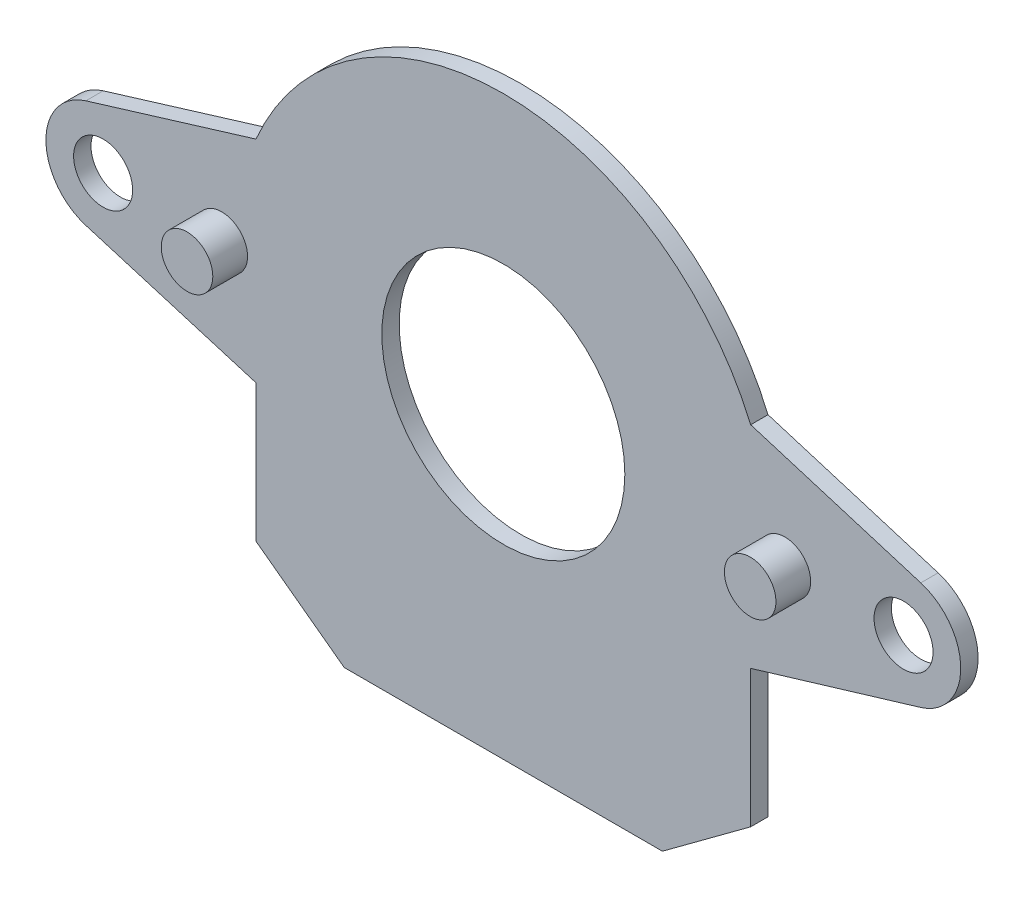
SolidWorks part; units mm, degrees
material "PETG"
ref_plane "Front Plane" through (0, 0, 0) normal (0, 0, 1) x (1, 0, 0)
ref_plane "Top Plane" through (0, 0, 0) normal (0, 1, 0) x (1, 0, 0)
ref_plane "Right Plane" through (0, 0, 0) normal (1, 0, 0) x (0, 0, -1)
sketch "Sketch1" plane through (0, 0, 0) normal (0, 0, 1) x (1, 0, 0)
  line L1 (14.25, -13.9625) -> (14.25, 6.0982)
  line L2 (-14.25, -13.9625) -> (-14.25, 6.0982)
  line L3 (-14.25, -13.9625) -> (-9.165, -17.722)
  line L4 (-9.165, -17.722) -> (9.165, -17.722)
  line L5 (9.165, -17.722) -> (14.25, -13.9625)
  line L6 (-14.25, -6.056) -> (-24.0362, -3.1122)
  line L7 (0, 3.4797) -> (0, 50003.4797) construction
  line L8 (-24.0485, 3.1085) -> (-14.25, 6.0982)
  line L9 (24.0485, 3.1085) -> (14.25, 6.0982)
  line L10 (14.25, -6.056) -> (24.0362, -3.1122)
  arc A0 (14.25, 6.0982) -> (-14.25, 6.0982) centre (0, 0) ccw
  circle A1 centre (0, 0) radius 7
  arc A2 (-24.0485, 3.1085) -> (-24.0362, -3.1122) centre (-23.1, 0) ccw
  arc A3 (24.0485, 3.1085) -> (24.0362, -3.1122) centre (23.1, 0) cw
  dimension "D1" = 28.5
  dimension "D2" = 15.5
  dimension "D7" = 14
  dimension "D8" = 6.056
  dimension "D10" = 3.25
  dimension "D4" = 17.722
  dimension "D5" = 13.9625
  dimension "D6" = 18.33
  dimension "D9" = 23.1
extrude "Boss-Extrude1" add sketch "Sketch1" along normal blind 1 contours L4 L7 A1 A0 L2 L3 | L8 A2 L6 L2 | L7 L4 L5 L1 A0 A1 | A3 L9 L1 L10 region at (11.4473, -15.4903, 0) region at (19.2892, 0.0104, 0) region at (-19.2892, 0.0104, 0)
sketch "Sketch2" plane through (0, 0, 1) normal (0, 0, 1) x (1, 0, 0)
  line L0 (0, -1.1396) -> (0, 49998.8604) construction
  circle A6 centre (-16.22, 0) radius 1.485
  circle A7 centre (-23.055, 0) radius 1.7
  circle A8 centre (23.055, 0) radius 1.7
  circle A9 centre (16.22, 0) radius 1.485
  dimension "D1" = 2.97
  dimension "D2" = 3.4
  dimension "D3" = 23.055
  dimension "D4" = 16.22
extrude "Boss-Extrude2" add sketch "Sketch2" along normal blind 2 contours A6 | A9 region at (-16.22, 0, 1)
extrude "Cut-Extrude1" cut sketch "Sketch2<5>" against normal through all contours A7 | A8 region at (-23.055, 0, 1) region at (23.055, 0, 1)
sketch "Sketch2<5>" plane through (0, 0, 1) normal (0, 0, 1) x (1, 0, 0) same geometry as "Sketch2"
equation "\"tol_dia_id_intfc\" = 0.0200mm ' For hole diameters - Interference fit"
equation "\"tol_dia_id_slip\"  = 0.0300mm ' For hole diameters - Slip fit"
equation "\"tol_dia_id_clear\" = 0.0500mm ' For hole diameters - Clearance fit"
equation "\"tol_dia_od_intfc\" = 0.0200mm ' For shaft diameters - Interference fit"
equation "\"tol_dia_od_slip\"  = 0.0300mm ' For shaft diameters - Slip fit"
equation "\"tol_dia_od_clear\" = 0.0500mm ' For shaft diameters - Clearance fit"
equation "\"tol_general_intfc\"= 0.0030mm ' For general parts (Horiz) - Interference fit"
equation "\"tol_general_slip\" = 0.0050mm ' For general parts (Horiz) - Slip fit"
equation "\"tol_general_clear\"= 0.0100mm ' For general parts (Horiz) - Clearance fit"
equation "\"tol_layer_intfc\"  = 0.0030mm ' For all parts (Vert) - Interference fit"
equation "\"tol_layer_slip\"   = 0.0050mm ' For all parts (Vert) - Slip fit"
equation "\"tol_layer_clear\"  = 0.0100mm ' For all parts (Vert) - Clearance fit"
equation "\"tol_corner_rad\"   = 0.100mm ' For corners that fit into other parts"
equation "\"D1@Sketch2\"=3-\"tol_dia_od_slip\""
